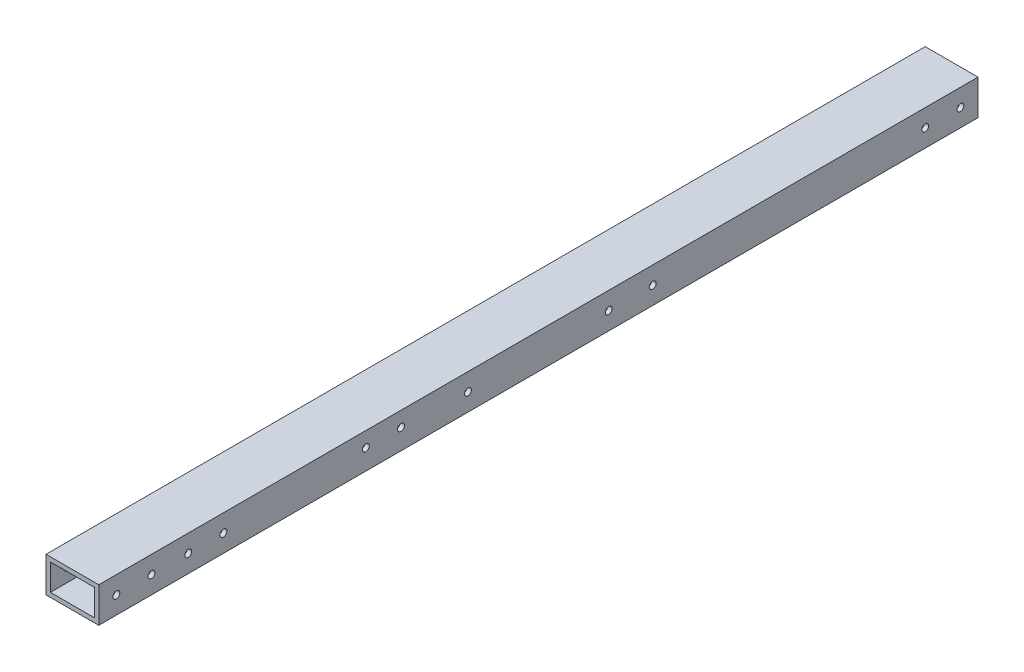
SolidWorks part; units mm, degrees
material "1060 Alloy"
ref_plane "Front Plane" through (0, 0, 0) normal (0, 0, 1) x (1, 0, 0)
ref_plane "Top Plane" through (0, 0, 0) normal (0, 1, 0) x (1, 0, 0)
ref_plane "Right Plane" through (0, 0, 0) normal (1, 0, 0) x (0, 0, -1)
sketch "Sketch1" plane through (0, 0, 0) normal (0, 0, 1) x (1, 0, 0)
  line L0 (-15.875, 9.525) -> (15.875, 9.525)
  line L2 (-19.05, 12.7) -> (19.05, 12.7)
  line L3 (-19.05, 12.7) -> (-19.05, -12.7)
  line L4 (-19.05, -12.7) -> (19.05, -12.7)
  line L5 (19.05, 12.7) -> (19.05, -12.7)
  line L10 (15.875, 9.525) -> (15.875, -9.525)
  line L11 (-15.875, -9.525) -> (15.875, -9.525)
  line L12 (-15.875, 9.525) -> (-15.875, -9.525)
  point P12 (0, 12.7)
  point P14 (19.05, 0)
  dimension "Wall Thickness" = 3.175
  dimension "Outside Width" = 38.1
  dimension "Outside Height" = 25.4
  dimension "Inside Height" = 19.05
  dimension "Inside Width" = 31.75
sketch "Sketch2" plane through (0, 0, 0) normal (1, 0, 0) x (0, 0, -1)
  line L0 (317.5, 0) -> (-317.5, 0)
  point P4 (0, 0)
  point P7 (-317.5, 0)
  point P10 (317.5, 0)
  dimension "Length" = 635
sketch "Sketch3" plane through (0, 0, 0) normal (0, 0, 1) x (1, 0, 0)
  line L21 (19.05, 12.7) -> (-19.05, 12.7)
  line L22 (19.05, -12.7) -> (19.05, 12.7)
  line L23 (-19.05, -12.7) -> (19.05, -12.7)
  line L24 (-19.05, 12.7) -> (-19.05, -12.7)
  line L25 (19.05, 12.7) -> (-19.05, 12.7)
  line L26 (19.05, -12.7) -> (19.05, 12.7)
  line L27 (-19.05, -12.7) -> (19.05, -12.7)
  line L28 (-19.05, 12.7) -> (-19.05, -12.7)
  line L29 (15.875, 9.525) -> (-15.875, 9.525)
  line L30 (15.875, -9.525) -> (15.875, 9.525)
  line L31 (-15.875, -9.525) -> (15.875, -9.525)
  line L32 (-15.875, 9.525) -> (-15.875, -9.525)
  line L33 (15.875, 9.525) -> (-15.875, 9.525)
  line L34 (15.875, -9.525) -> (15.875, 9.525)
  line L35 (-15.875, -9.525) -> (15.875, -9.525)
  line L36 (-15.875, 9.525) -> (-15.875, -9.525)
  dimension "D1" = 0
  dimension "D2" = 0
extrude "Boss-Extrude1" add sketch "Sketch3" along normal up to vertex (317.5 mm away) and the other way up to vertex (317.5 mm away) up to point (0, 0, 317.5) other way up to point (0, 0, -317.5)
sketch "Drawing Reference" plane through (0, 0, 0) normal (1, 0, 0) x (0, 0, -1)
  line L0 (-317.5, 0) -> (317.5, 0) construction
  line L1 (0, -12.7) -> (0, 12.7) construction
  line L2 (-317.5, -12.7) -> (317.5, -12.7) construction
  line L5 (-317.5, 12.7) -> (317.5, 12.7) construction
  point P7 (-290.068, 0)
  point P8 (290.068, 0)
  dimension "D1" = 27.432
sketch "Sketch4" plane through (-19.05, 0, 0) normal (-1, 0, 0) x (0, 0, 1)
  line L0 (-317.5, 0) -> (-304.8, 0)
  line L1 (-317.5, 12.7) -> (-317.5, -12.7) construction
  line L2 (-304.8, 0) -> (-279.4, 0)
  line L3 (317.5, 12.7) -> (317.5, -12.7) construction
  line L4 (317.5, 0) -> (304.8, 0)
  line L5 (304.8, 0) -> (279.4, 0)
  line L6 (0, 0) -> (50.8, 0) construction
  line L7 (0, 0) -> (-50.8, 0) construction
  point P11 (-304.8, 0)
  point P13 (-279.4, 0)
  point P14 (304.8, 0)
  point P15 (279.4, 0)
hole_wizard "#10 Clearance Hole2" positions "Sketch11" profile "Sketch12" hole size "#10" standard "ANSI Inch" end condition through all
sketch "Sketch11" plane through (-19.05, 0, 0) normal (-1, 0, 0) x (0, 0, 1)
  point P0 (-304.8, 0)
  point P3 (-279.4, 0)
  point P6 (279.4, 0)
  point P9 (304.8, 0)
sketch "Sketch12" plane through (-19.05, 0, -304.8) normal (0, 1, 0) x (0, 0, 1)
  line L0 (0, 0) -> (0, 38.1)
  line L1 (0, 38.1) -> (2.4892, 38.1)
  line L2 (2.4892, 38.1) -> (2.4892, 0)
  line L5 (2.4892, 0) -> (0, 0)
  line L11 (0, -6.35) -> (0, 107.95) construction
  dimension "Thru Hole Dia." = 4.9784
  dimension "Thru Hole Depth" = 38.1
hole_wizard "#10 Clearance Hole4" positions "Sketch14" profile "Sketch16" hole size "#10" standard "ANSI Inch" end condition through all
sketch "Sketch14" plane through (19.05, 0, 0) normal (1, 0, 0) x (0, 0, -1)
  point P33 (-252.857, 0)
  point P36 (-227.457, 0)
  point P42 (-124.587, 1.9434)
  point P45 (-99.187, 1.9434)
sketch "Sketch16" plane through (19.05, 0, 252.857) normal (0, 1, 0) x (0, 0, -1)
  line L0 (0, 0) -> (0, 38.1)
  line L1 (0, 38.1) -> (2.4892, 38.1)
  line L2 (2.4892, 38.1) -> (2.4892, 0)
  line L5 (2.4892, 0) -> (0, 0)
  line L11 (0, -6.35) -> (0, 107.95) construction
  dimension "Thru Hole Dia." = 4.9784
  dimension "Thru Hole Depth" = 38.1
hole_wizard "#10 Clearance Hole3" positions "Sketch20" profile "Sketch21" hole size "#10" standard "ANSI Inch" end condition through all
sketch "Sketch20" plane through (-19.05, 0, 0) normal (-1, 0, 0) x (0, 0, 1)
  point P0 (-50.8, 0)
  point P3 (50.8, 0)
sketch "Sketch21" plane through (-19.05, 0, -50.8) normal (0, 1, 0) x (0, 0, 1)
  line L0 (0, 0) -> (0, 38.1)
  line L1 (0, 38.1) -> (2.4892, 38.1)
  line L2 (2.4892, 38.1) -> (2.4892, 0)
  line L5 (2.4892, 0) -> (0, 0)
  line L11 (0, -6.35) -> (0, 107.95) construction
  dimension "Thru Hole Dia." = 4.9784
  dimension "Thru Hole Depth" = 38.1
sketch "Sketch22" plane through (19.05, 0, 0) normal (1, 0, 0) x (0, 0, -1)
  line L0 (50.8, 0) -> (82.55, 0) construction
hole_wizard "#10 Clearance Hole5" positions "Sketch23" profile "Sketch24" hole size "#10" standard "ANSI Inch" end condition through all
sketch "Sketch23" plane through (19.05, 0, 0) normal (1, 0, 0) x (0, 0, -1)
  point P0 (82.55, 0)
sketch "Sketch24" plane through (19.05, 0, -82.55) normal (0, 1, 0) x (0, 0, -1)
  line L0 (0, 0) -> (0, 38.1)
  line L1 (0, 38.1) -> (2.4892, 38.1)
  line L2 (2.4892, 38.1) -> (2.4892, 0)
  line L5 (2.4892, 0) -> (0, 0)
  line L11 (0, -6.35) -> (0, 107.95) construction
  dimension "Thru Hole Dia." = 4.9784
  dimension "Thru Hole Depth" = 38.1
equation "\"D1@Drawing Reference\"=\"Outside Width@Sketch1\" * 0.72"
